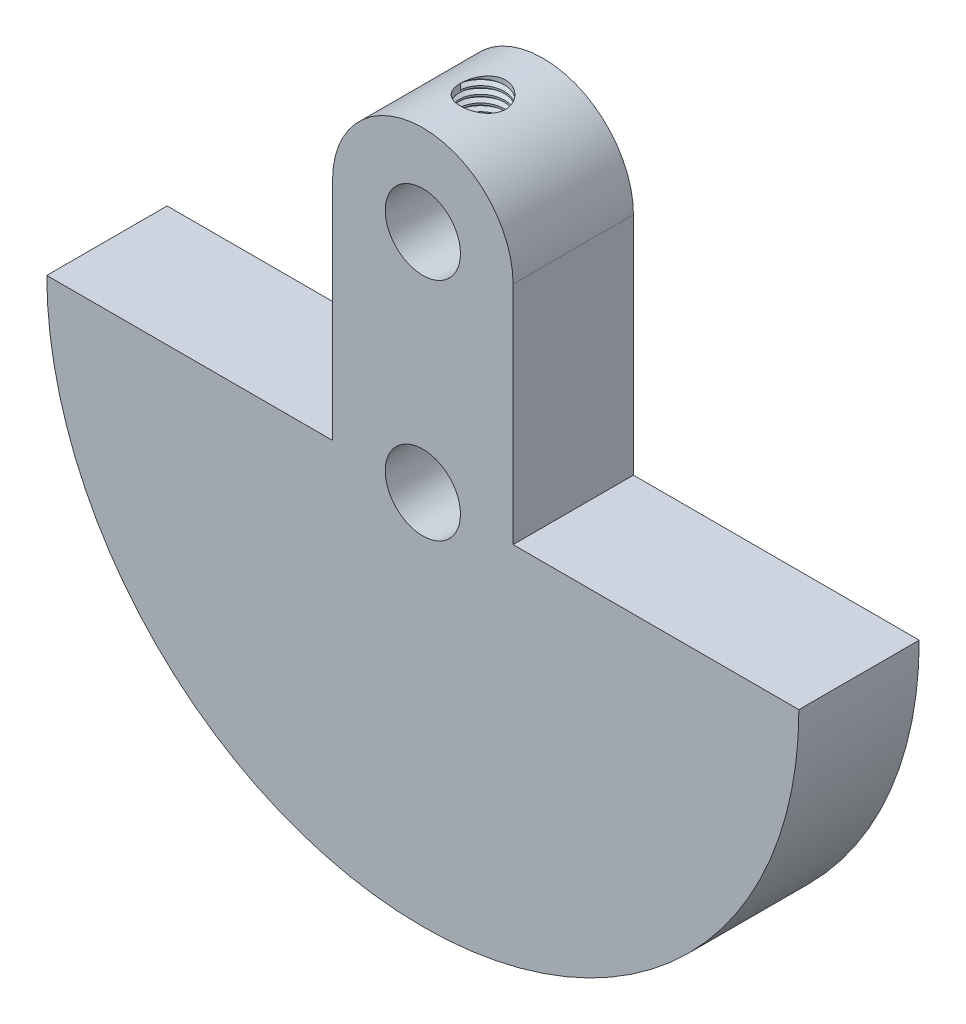
SolidWorks part; units mm, degrees
ref_plane "Front Plane" through (0, 0, 0) normal (0, 0, 1) x (1, 0, 0)
ref_plane "Top Plane" through (0, 0, 0) normal (0, 1, 0) x (1, 0, 0)
ref_plane "Right Plane" through (0, 0, 0) normal (1, 0, 0) x (0, 0, -1)
sketch "Sketch1" plane through (0, 0, 0) normal (0, 0, 1) x (1, 0, 0)
  line L0 (0, 0) -> (0, 15) construction
  line L1 (-6, 0) -> (-6, 15)
  line L2 (6, 0) -> (6, 15)
  line L3 (-25, 0) -> (-6, 0)
  line L4 (6, 0) -> (25, 0)
  circle A0 centre (0, 0) radius 25
  arc A2 (6, 15) -> (-6, 15) centre (0, 15) ccw
  circle A3 centre (0, 0) radius 2.5
  circle A4 centre (0, 15) radius 2.5
  point P4 (0, 7.5)
  dimension "D1" = 50
  dimension "D4" = 5
  dimension "D2" = 12
  dimension "D3" = 15
extrude "Boss-Extrude1" add sketch "Sketch1" along normal blind 8 contours L2 A2 L1 L3 A0 L4 A3 A4 region at (0, -7.0982, 0)
ref_plane "Plane1" through (0, 21, 0) normal (0, 1, 0) x (1, 0, 0)
sketch "Sketch2" plane through (0, 21, 0) normal (0, 1, 0) x (1, 0, 0)
  line L0 (6, -8) -> (6, 0) construction
  circle A0 centre (0, -4) radius 1.5
  dimension "D1" = 3
  dimension "D2" = 4
  dimension "D3" = 6
extrude "Cut-Extrude1" cut sketch "Sketch2" against normal blind 5
thread "Thread1" pitch 0.5 method cut profile "Thread Profile1" start angle 0, offset 0.2, length 0, pitch 0.5, diameter 3
ref_plane "Plane2" through (-1.5, 20.8, 4) normal (0, 0, 1) x (-1, 0, 0)
sketch "Thread Profile1" plane through (-1.5, 20.8, 4) normal (0, 0, 1) x (-1, 0, 0)
  line L0 (0, 0) -> (0, 0.5) construction
  line L1 (0, 0) -> (0.2706, 0.1562)
  line L2 (0.2706, 0.1562) -> (0.2706, 0.2187)
  line L3 (0.2706, 0.2187) -> (0, 0.375)
  line L4 (0.2706, 0.1875) -> (0, 0.1875) construction
  line L11 (0, 0) -> (0, 0.375)
  point P2 (0, 0)
  dimension "Pitch" = 0.5
  dimension "Profile_Angle" = 60
  dimension "Profile_Land" = 0.0625
  dimension "Profile_Height" = 0.2706
